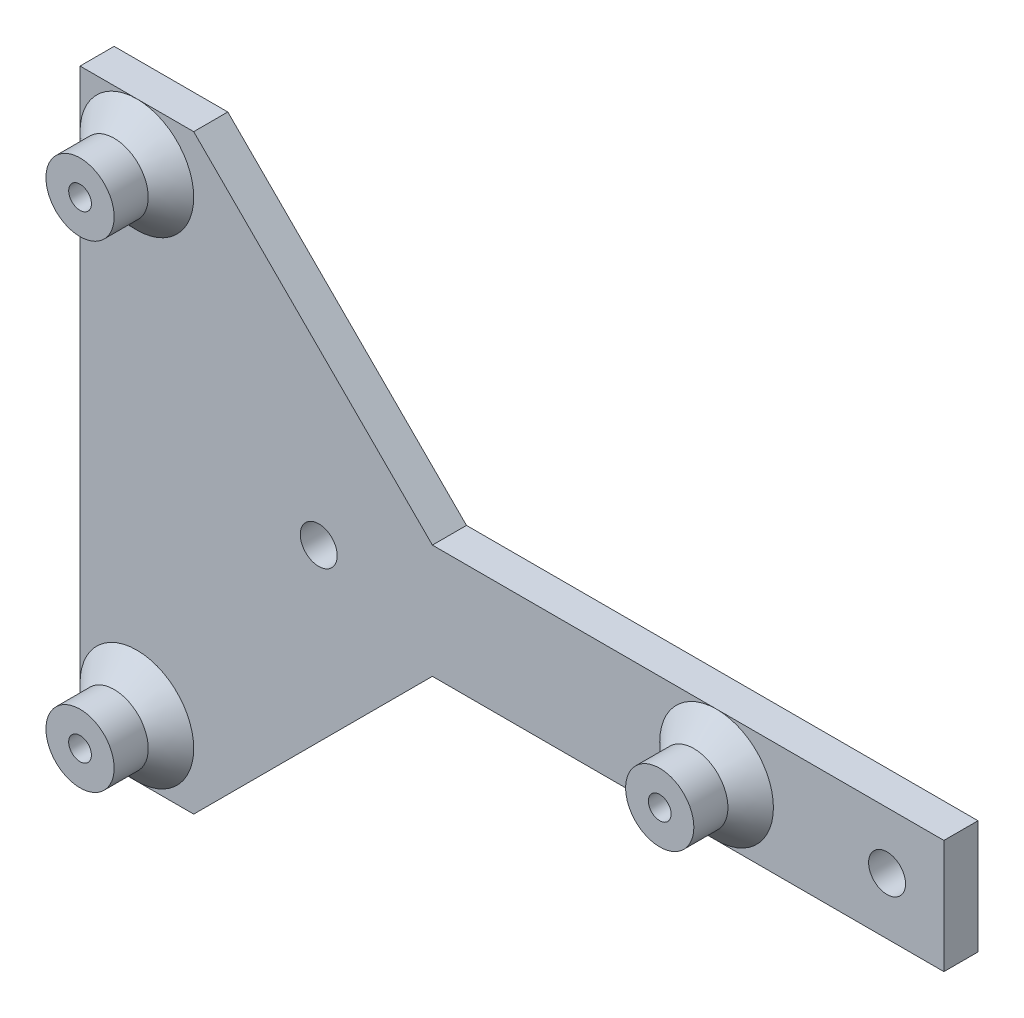
SolidWorks part; units mm, degrees
ref_plane "Alzado" through (0, 0, 0) normal (0, 0, 1) x (1, 0, 0)
ref_plane "Planta" through (0, 0, 0) normal (0, 1, 0) x (1, 0, 0)
ref_plane "Vista lateral" through (0, 0, 0) normal (1, 0, 0) x (0, 0, -1)
sketch "Croquis1" plane through (0, 0, 0) normal (0, 0, 1) x (1, 0, 0)
  line L1 (-5, 5) -> (5, 5)
  line L2 (-5, 5) -> (-5, -5)
  line L3 (-5, -5) -> (5, -5)
  line L4 (5, 5) -> (5, -5)
  line L5 (-5, 5) -> (5, -5) construction
  line L6 (-5, -5) -> (5, 5) construction
  line L7 (-55, 5) -> (-45, 5)
  line L8 (-55, 5) -> (-55, -5)
  line L9 (-55, -5) -> (-45, -5)
  line L10 (-45, 5) -> (-45, -5)
  line L11 (-55, 5) -> (-45, -5) construction
  line L12 (-55, -5) -> (-45, 5) construction
  circle A0 centre (0, 0) radius 1.625
  circle A1 centre (-50, 0) radius 1.625
  dimension "D2" = 3.25
  dimension "D3" = 3.25
  dimension "D4" = 10
  dimension "D1" = 50
  dimension "D5" = 10
  dimension "D6" = 10
  dimension "D7" = 10
extrude "Saliente-Extruir1" add sketch "Croquis1" along normal blind 3
sketch "Croquis2" plane through (0, 0, 3) normal (0, 0, 1) x (1, 0, 0)
  line L0 (-55, -5) -> (-45, -5) construction
  line L1 (-5, 5) -> (-45, 5)
  line L2 (-5, 5) -> (-5, -5)
  line L3 (-5, -5) -> (-45, -5)
  line L4 (-45, 5) -> (-45, -5)
  line L5 (-45, -5) -> (-45, 5) construction
  line L6 (-61, -5) -> (-61, -26)
  line L7 (-55, 5) -> (-61, 5)
  line L8 (-55, 5) -> (-55, -5)
  line L9 (-55, -5) -> (-61, -5)
  line L11 (-71, 26) -> (-61, 26)
  line L12 (-71, 26) -> (-71, -26)
  line L13 (-71, -26) -> (-61, -26)
  line L14 (-61, 26) -> (-61, 5)
  circle A0 centre (-15, 0) radius 1
  circle A1 centre (-66, 21) radius 1
  circle A2 centre (-66, -21) radius 1
  circle A3 centre (0, 0) radius 1.625 construction
  dimension "D7" = 5
  dimension "D8" = 5
  dimension "D9" = 2
  dimension "D10" = 2
  dimension "D11" = 2
  dimension "D1" = 15
  dimension "D2" = 51
  dimension "D3" = 21
  dimension "D4" = 21
  dimension "D5" = 10
  dimension "D6" = 5
extrude "Saliente-Extruir2" add sketch "Croquis2" against normal blind 3
sketch "Croquis3" plane through (0, 0, 3) normal (0, 0, 1) x (1, 0, 0)
  circle A0 centre (-66, 21) radius 1
  circle A1 centre (-66, 21) radius 3
  circle A2 centre (-66, -21) radius 1
  circle A3 centre (-66, -21) radius 3
  circle A4 centre (-15, 0) radius 1
  circle A5 centre (-15, 0) radius 3
  dimension "D1" = 2
  dimension "D2" = 6
  dimension "D3" = 6
  dimension "D4" = 6
extrude "Saliente-Extruir3" add sketch "Croquis3" along normal blind 5
chamfer "Chaflán1" distance 2 angle 45 3 edges at (-12, 0, 3) (-63, 21, 3) (-63, -21, 3)
chamfer "Chaflán2" distance 21 angle 45 2 edges at (-61, 5, 1.5) (-61, -5, 1.5)
